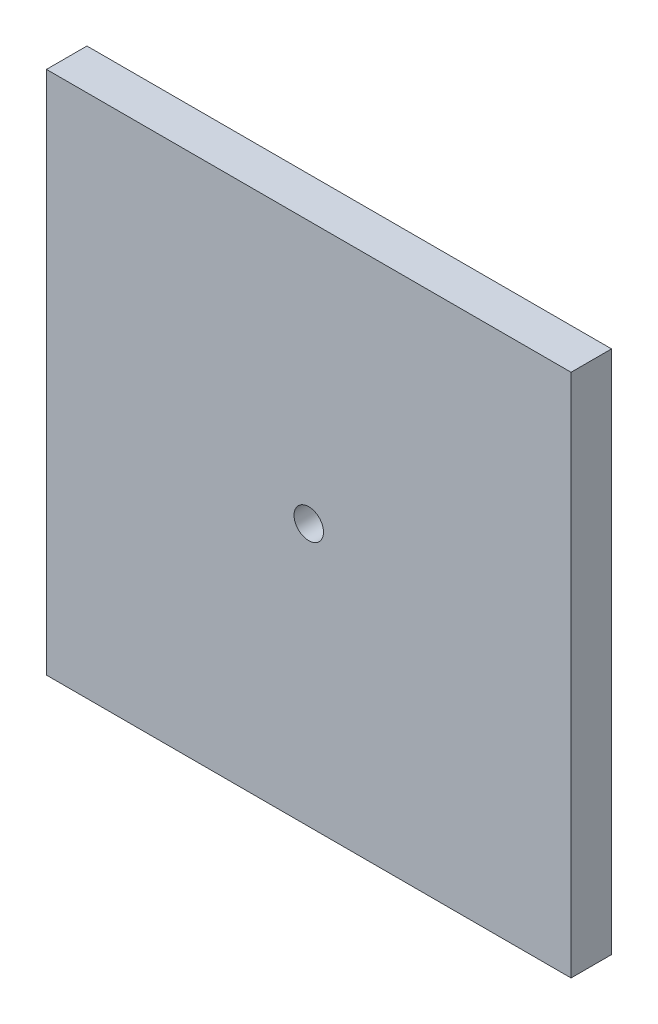
SolidWorks part; units mm, degrees
ref_plane "Front Plane" through (0, 0, 0) normal (0, 0, 1) x (1, 0, 0)
ref_plane "Top Plane" through (0, 0, 0) normal (0, 1, 0) x (1, 0, 0)
ref_plane "Right Plane" through (0, 0, 0) normal (1, 0, 0) x (0, 0, -1)
sketch "Sketch1" plane through (0, 0, 0) normal (0, 0, 1) x (1, 0, 0)
  line L0 (0, 0) -> (-14.3341, -39.3825) construction
  line L1 (-56.5785, 56.5785) -> (56.5785, 56.5785)
  line L2 (-56.5785, 56.5785) -> (-56.5785, -56.5785)
  line L3 (-56.5785, -56.5785) -> (56.5785, -56.5785)
  line L4 (56.5785, 56.5785) -> (56.5785, -56.5785)
  line L5 (0, 0) -> (0, -51.5938) construction
  line L6 (-27.4443, 51.5938) -> (31.5245, 51.5938) construction
  circle A0 centre (0, 0) radius 51.5938
  circle A1 centre (-14.3341, -39.3825) radius 3.175
  circle A2 centre (0, 0) radius 3.175
  circle A3 centre (-26.9392, 32.1049) radius 3.175
  circle A4 centre (41.2733, 7.2776) radius 3.175
  circle A5 centre (-43.8785, 43.8785) radius 3.175
  circle A6 centre (43.8785, 43.8785) radius 3.175
  circle A7 centre (43.8785, -43.8785) radius 3.175
  circle A8 centre (-43.8785, -43.8785) radius 3.175
  point P12 (0, 56.5785)
  point P18 (0, 0)
  point P23 (-56.5785, 0)
  point P29 (0, 0)
  dimension "D1" = 103.1875
  dimension "D4" = 6.35
  dimension "D5" = 6.35
  dimension "D7" = 6.35
  dimension "D2" = 41.91
  dimension "D3" = 20
  dimension "D8" = 12.7
  dimension "D9" = 90
  dimension "D10" = 12.7
  dimension "D11" = 4
  dimension "D12" = 56.5785
  dimension "D13" = 4.9847
  dimension "D6" = 3
extrude "Boss-Extrude1" add sketch "Sketch1" along normal blind 8.7312 contours L4 L1 L2 L3 A8 A7 A6 A5 A0 | A6 | A5 | A8 | A7 | A1 | A3 | A4 | A0 A4 A3 A2 A1 region at (0, 54.9782, 0) region at (-50.1345, 0, 0) region at (-14.3341, -39.3825, 0) region at (-26.9392, 32.1049, 0) region at (41.2733, 7.2776, 0) region at (-43.8785, 43.8785, 0) region at (43.8785, 43.8785, 0) region at (43.8785, -43.8785, 0) region at (-43.8785, -43.8785, 0)
extrude "Boss-Extrude4" add sketch "Sketch1<5>" against normal blind 9.398 contours A6 | A5 | A8 | A7 region at (-43.8785, 43.8785, 0) region at (43.8785, 43.8785, 0) region at (43.8785, -43.8785, 0) region at (-43.8785, -43.8785, 0)
sketch "Sketch1<5>" plane through (0, 0, 0) normal (0, 0, 1) x (1, 0, 0) same geometry as "Sketch1"
